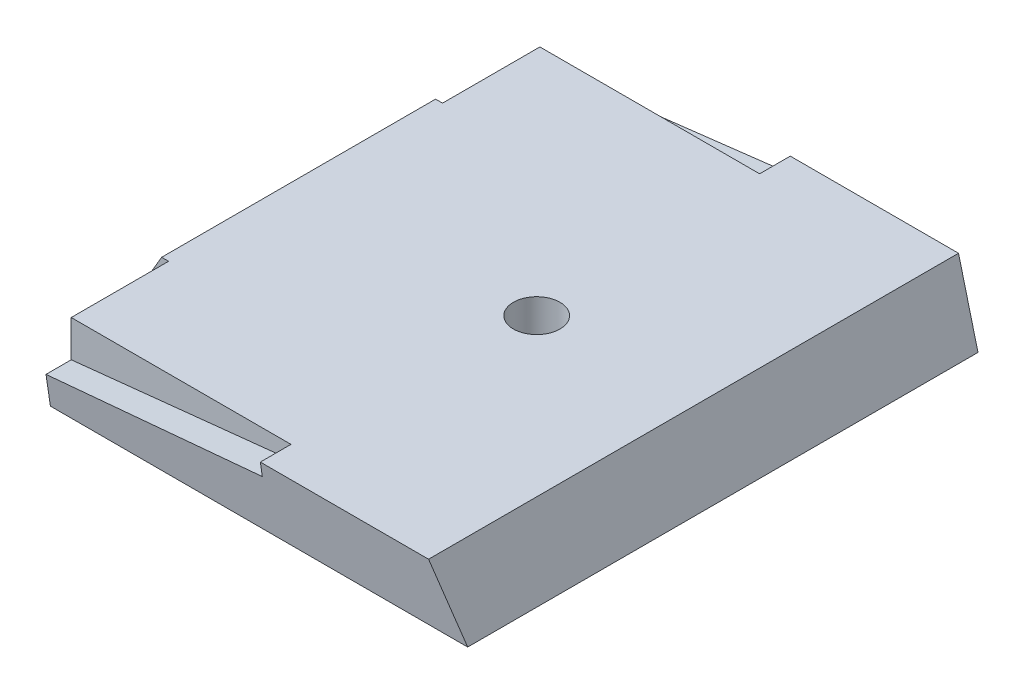
SolidWorks part; units mm, degrees
ref_plane "Front Plane" through (0, 0, 0) normal (0, 0, 1) x (1, 0, 0)
ref_plane "Top Plane" through (0, 0, 0) normal (0, 1, 0) x (1, 0, 0)
ref_plane "Right Plane" through (0, 0, 0) normal (1, 0, 0) x (0, 0, -1)
sketch "Sketch1" plane through (0, 0, 0) normal (0, 1, 0) x (1, 0, 0)
  line L1 (0, 0) -> (-63.22, 0)
  line L2 (0, 0) -> (0, -72.35)
  line L3 (0, -72.35) -> (-63.22, -72.35)
  line L4 (-63.22, 0) -> (-63.22, -72.35)
  dimension "D1" = 72.35
  dimension "D2" = 63.22
extrude "Boss-Extrude1" add sketch "Sketch1" along normal blind 9.06
sketch "Sketch2" plane through (0, 0, 72.35) normal (0, 0, 1) x (1, 0, 0)
  line L0 (-63.22, 9.06) -> (-57.92, 9.06)
  line L1 (-63.22, 9.06) -> (0, 9.06) construction
  line L2 (-57.92, 9.06) -> (-63.22, 0)
  line L3 (-63.22, 9.06) -> (-63.22, 0) construction
  line L4 (-63.22, 0) -> (-63.22, 9.06)
  dimension "D1" = 5.3
extrude "Cut-Extrude1" cut sketch "Sketch2" against normal up to next
sketch "Sketch3" plane through (0, 0, 0) normal (0, -1, 0) x (1, 0, 0)
  line L1 (-63.22, 72.35) -> (-56.97, 72.35)
  line L2 (-63.22, 72.35) -> (-63.22, 54.875)
  line L3 (-63.22, 54.875) -> (-56.97, 54.875)
  line L4 (-56.97, 72.35) -> (-56.97, 54.875)
  line L5 (-63.22, 0) -> (-56.97, 0)
  line L6 (-63.22, 0) -> (-63.22, 17.475)
  line L7 (-63.22, 17.475) -> (-56.97, 17.475)
  line L8 (-56.97, 0) -> (-56.97, 17.475)
  dimension "D1" = 37.4
  dimension "D2" = 17.475
  dimension "D3" = 6.25
extrude "Cut-Extrude2" cut sketch "Sketch3" against normal up to next
sketch "Sketch4" plane through (0, 0, 72.35) normal (0, 0, 1) x (1, 0, 0)
  line L0 (-56.97, 9.06) -> (-56.97, 4.06)
  line L1 (-56.97, 9.06) -> (-56.97, 0) construction
  line L2 (-56.97, 4.06) -> (-26.97, 7.21)
  line L3 (-26.97, 7.21) -> (-26.97, 9.06)
  line L4 (-56.97, 9.06) -> (0, 9.06) construction
  line L5 (-26.97, 9.06) -> (-56.97, 9.06)
  dimension "D1" = 30
  dimension "D2" = 5
  dimension "D3" = 1.85
extrude "Cut-Extrude3" cut sketch "Sketch4" against normal blind 4.185
extrude "Cut-Extrude4" cut sketch "Sketch4<2>" along normal blind 4.185 from surface starting at face at (-28.485, 4.53, 0)
sketch "Sketch4<2>" plane through (0, 0, 72.35) normal (0, 0, 1) x (1, 0, 0) same geometry as "Sketch4"
sketch "Sketch7" plane through (0, 0, 72.35) normal (0, 0, 1) x (1, 0, 0)
  line L0 (0, 0) -> (-4, 9.06)
  line L1 (-26.97, 9.06) -> (0, 9.06) construction
  line L2 (-4, 9.06) -> (0, 9.06)
  line L3 (0, 9.06) -> (0, 0)
  dimension "D1" = 4
extrude "Cut-Extrude6" cut sketch "Sketch7" against normal up to next
sketch "Sketch8" plane through (-56.97, 0, 0) normal (-1, 0, 0) x (0, 0, 1)
  line L0 (72.35, 0) -> (71.01, 0)
  line L1 (54.875, 0) -> (72.35, 0) construction
  line L2 (71.01, 0) -> (72.35, 9.06)
  line L3 (72.35, 9.06) -> (72.35, 0)
  line L4 (0, 0) -> (1.34, 0)
  line L5 (0, 0) -> (17.475, 0) construction
  line L6 (1.34, 0) -> (0, 9.06)
  line L7 (0, 9.06) -> (0, 0)
  dimension "D1" = 9.06
  dimension "D2" = 1.34
  dimension "D3" = 1.34
  dimension "D4" = 9.06
extrude "Cut-Extrude7" cut sketch "Sketch8" against normal up to next
sketch "Sketch9" plane through (0, 0, 0) normal (0, -1, 0) x (1, 0, 0)
  line L0 (0, 71.01) -> (-56.97, 71.01) construction
  line L2 (0, 71.01) -> (0, 1.34) construction
  line L5 (-22.2692, 41.692) -> (-28.6199, 41.6579)
  line L6 (-28.6199, 41.6579) -> (-31.7658, 36.1409)
  line L7 (-31.7658, 36.1409) -> (-28.5608, 30.658)
  line L8 (-28.5608, 30.658) -> (-22.2101, 30.6921)
  line L9 (-22.2101, 30.6921) -> (-19.0642, 36.2091)
  line L10 (-19.0642, 36.2091) -> (-22.2692, 41.692)
  circle A0 centre (-25.415, 36.175) radius 3.175
  circle A1 centre (-25.415, 36.175) radius 5.5 construction
  dimension "D3" = 6.35
  dimension "D1" = 34.835
  dimension "D2" = 25.415
extrude "Cut-Extrude8" cut sketch "Sketch9" against normal up to next contours A0 region at (-25.415, 0, 36.175)
extrude "Cut-Extrude9" cut sketch "Sketch9<3>" against normal blind 4.3
sketch "Sketch9<3>" plane through (0, 0, 0) normal (0, -1, 0) x (1, 0, 0) same geometry as "Sketch9"
